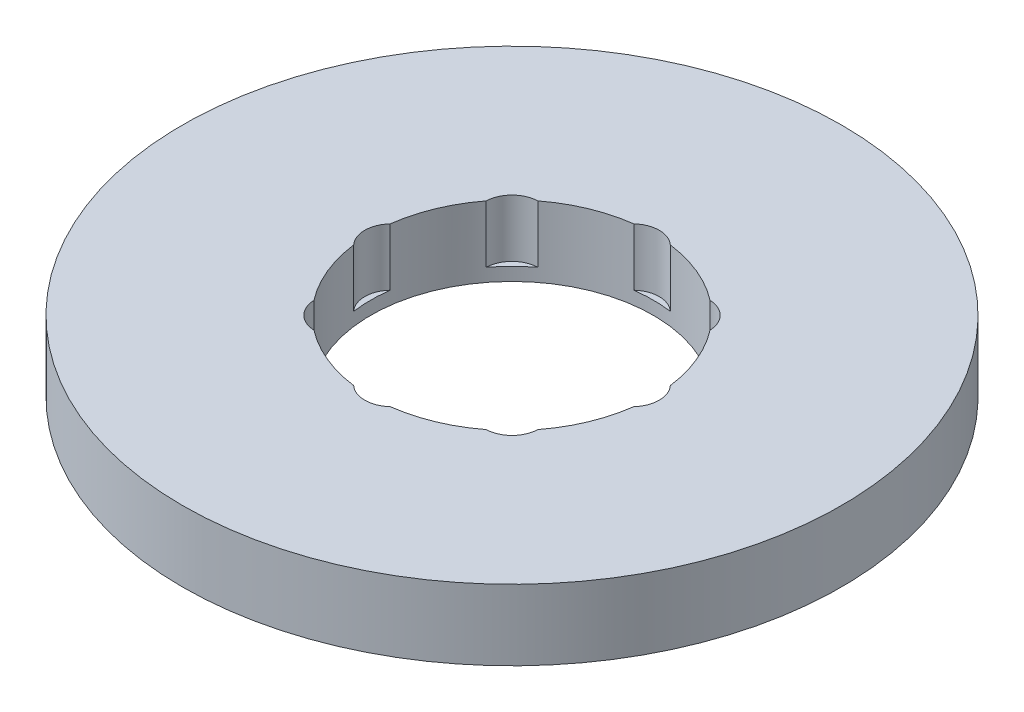
SolidWorks part; units mm, degrees
ref_plane "Front Plane" through (0, 0, 0) normal (0, 0, 1) x (1, 0, 0)
ref_plane "Top Plane" through (0, 0, 0) normal (0, 1, 0) x (1, 0, 0)
ref_plane "Right Plane" through (0, 0, 0) normal (1, 0, 0) x (0, 0, -1)
sketch "Sketch1" plane through (0, 0, 0) normal (0, 1, 0) x (1, 0, 0)
  circle A0 centre (0, 0) radius 70
  dimension "FLANGE_OD" = 140
extrude "Boss-Extrude1" add sketch "Sketch1" along normal blind 15
sketch "Sketch2" plane through (0, 0, 0) normal (0, 1, 0) x (1, 0, 0)
  circle A0 centre (0, 0) radius 30
  dimension "BORE_D" = 60
extrude "Cut-Extrude1" cut sketch "Sketch2" along normal through all
sketch "Sketch3" plane through (0, 15, 0) normal (0, 1, 0) x (1, 0, 0)
  circle A0 centre (0, 0) radius 25.565 construction
  circle A1 centre (-25.565, 0) radius 5.7053
  dimension "BOLT_D" = 11.4106
  dimension "BOLT_PCD" = 51.1299
extrude "Cut-Extrude2" cut sketch "Sketch3" against normal blind 12.2072
pattern_circular "CirPattern1" count 8 over 360 about axis through (0, 0, 0) along (0, 1, 0) of "Cut-Extrude2"
